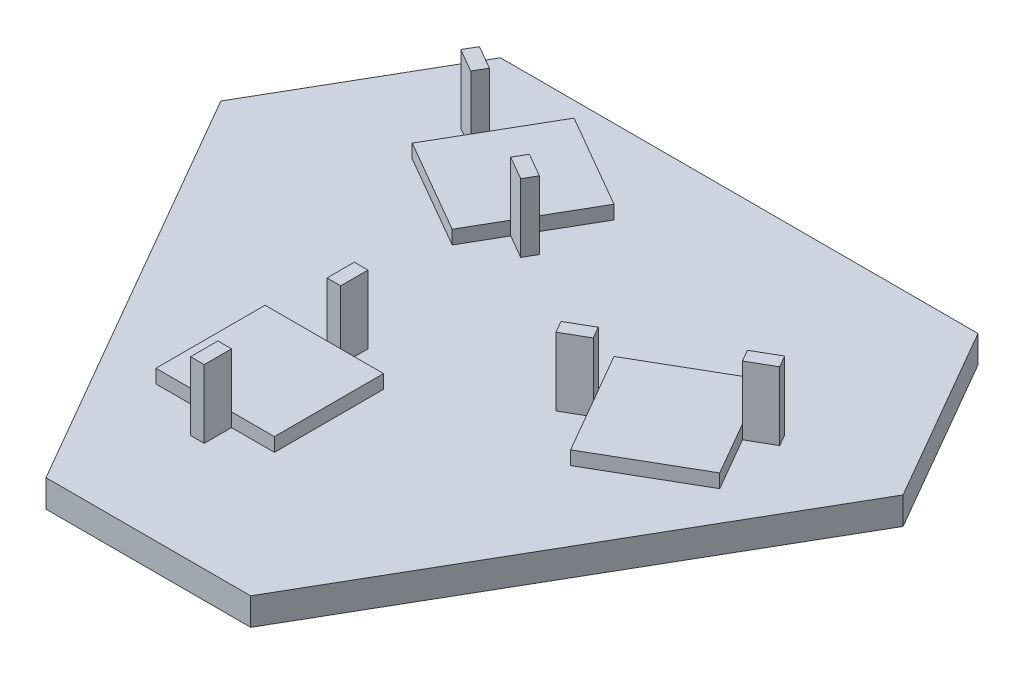
SolidWorks part; units mm, degrees
ref_plane "Front Plane" through (0, 0, 0) normal (0, 0, 1) x (1, 0, 0)
ref_plane "Top Plane" through (0, 0, 0) normal (0, 1, 0) x (1, 0, 0)
ref_plane "Right Plane" through (0, 0, 0) normal (1, 0, 0) x (0, 0, -1)
sketch "Sketch1" plane through (0, 0, 0) normal (0, 1, 0) x (1, 0, 0)
  line L14 (-106.25, 184.0304) -> (81.25, 75.7772) construction
  line L15 (87.5, 216.5064) -> (-87.5, 216.5064)
  line L16 (-87.5, 216.5064) -> (-125, 151.5544)
  line L17 (-125, 151.5544) -> (-37.5, 0)
  line L18 (-37.5, 0) -> (37.5, 0)
  line L19 (37.5, 0) -> (125, 151.5544)
  line L20 (125, 151.5544) -> (87.5, 216.5064)
  line L21 (106.25, 184.0304) -> (-81.25, 75.7772) construction
  line L22 (0, 216.5064) -> (0, 0) construction
  line L23 (87.5, 216.5064) -> (-37.5, 0) construction
  line L24 (-87.5, 216.5064) -> (37.5, 0) construction
  line L25 (125, 151.5544) -> (-125, 151.5544) construction
  point P1 (0, 216.5064)
  point P8 (0, 122.6869)
  dimension "D1" = 175
  dimension "D2" = 75
  dimension "D3" = 120
extrude "Boss-Extrude1" add sketch "Sketch1" along normal blind 10
sketch "Sketch2" plane through (0, 10, 0) normal (0, 1, 0) x (1, 0, 0)
  line L6 (-87.5, 216.5064) -> (-125, 151.5544) construction
  line L7 (125, 151.5544) -> (87.5, 216.5064) construction
  line L8 (-37.5, 0) -> (37.5, 0) construction
  line L16 (-36.9173, 148.2591) -> (-15.2173, 185.8446)
  line L17 (-36.9173, 148.2591) -> (-71.5583, 168.2591)
  line L18 (-15.2173, 185.8446) -> (-49.8583, 205.8446)
  line L19 (-71.5583, 168.2591) -> (-49.8583, 205.8446)
  line L20 (87.5, 216.5064) -> (-100, 108.2532) construction
  line L21 (-3.6875, 89.8727) -> (-47.0875, 89.8727)
  line L22 (-3.6875, 89.8727) -> (-3.6875, 49.8727)
  line L23 (-47.0875, 89.8727) -> (-47.0875, 49.8727)
  line L24 (-3.6875, 49.8727) -> (-47.0875, 49.8727)
  line L25 (87.5, 216.5064) -> (-87.5, 216.5064) construction
  line L26 (33.0863, 137.5314) -> (54.7863, 99.9459)
  line L27 (33.0863, 137.5314) -> (67.7273, 157.5314)
  line L28 (54.7863, 99.9459) -> (89.4273, 119.9459)
  line L29 (67.7273, 157.5314) -> (89.4273, 119.9459)
  line L30 (-37.5, 0) -> (-37.5, 216.5064) construction
  line L31 (-63.7083, 181.8557) -> (-72.3686, 186.8557)
  line L32 (-63.7083, 181.8557) -> (-61.2083, 186.1858)
  line L33 (-72.3686, 186.8557) -> (-69.8686, 191.1858)
  line L34 (-61.2083, 186.1858) -> (-69.8686, 191.1858)
  line L35 (-29.0673, 161.8557) -> (-20.407, 156.8557)
  line L36 (-29.0673, 161.8557) -> (-26.5673, 166.1858)
  line L37 (-20.407, 156.8557) -> (-17.907, 161.1858)
  line L38 (-26.5673, 166.1858) -> (-17.907, 161.1858)
  line L39 (84.2376, 148.9348) -> (75.5773, 143.9348)
  line L40 (84.2376, 148.9348) -> (86.7376, 144.6046)
  line L41 (75.5773, 143.9348) -> (78.0773, 139.6046)
  line L42 (86.7376, 144.6046) -> (78.0773, 139.6046)
  line L43 (32.2761, 118.9348) -> (40.9363, 123.9348)
  line L44 (32.2761, 118.9348) -> (34.7761, 114.6046)
  line L45 (40.9363, 123.9348) -> (43.4363, 119.6046)
  line L46 (34.7761, 114.6046) -> (43.4363, 119.6046)
  line L47 (-19.3875, 99.8727) -> (-19.3875, 89.8727)
  line L48 (-19.3875, 99.8727) -> (-24.3875, 99.8727)
  line L49 (-19.3875, 89.8727) -> (-24.3875, 89.8727)
  line L50 (-24.3875, 99.8727) -> (-24.3875, 89.8727)
  line L51 (-19.3875, 49.8727) -> (-19.3875, 39.8727)
  line L52 (-19.3875, 49.8727) -> (-24.3875, 49.8727)
  line L53 (-19.3875, 39.8727) -> (-24.3875, 39.8727)
  line L54 (-24.3875, 49.8727) -> (-24.3875, 39.8727)
  line L55 (-125, 151.5544) -> (-37.5, 0) construction
  line L56 (-87.5, 216.5064) -> (100, 108.2532) construction
  line L57 (37.5, 0) -> (125, 151.5544) construction
  dimension "D1" = 5
  dimension "D2" = 10
  dimension "D3" = 37.9295
  dimension "D4" = 46.6111
  dimension "D5" = 49.8727
  dimension "D6" = 40
  dimension "D7" = 43.4
  dimension "D8" = 22.7
  dimension "D9" = 22.7
  dimension "D10" = 22.7
  dimension "D11" = 22.7
  dimension "D12" = 22.7
  dimension "D13" = 22.7
  dimension "D14" = 33.8125
  dimension "D15" = 41.1875
  dimension "D16" = 9.5875
extrude "Boss-Extrude2" add sketch "Sketch2" along normal blind 5 contours L19 L17 L16 L18 | L24 L22 L21 L23 | L29 L27 L26 L28 region at (-43.3878, 10, -177.0519) region at (-25.3875, 10, -69.8727) region at (61.2568, 10, -128.7386)
extrude "Boss-Extrude3" add sketch "Sketch2<3>" along normal blind 25 contours L19 L34 L33 L31 | L38 L16 L35 L37 | L48 L50 L21 L47 | L24 L54 L53 L51 | L44 L46 L26 L43 | L42 L40 L39 L29 region at (-23.4872, 10, -161.5208) region at (-66.7884, 10, -186.5208) region at (-21.8875, 10, -94.8727) region at (-21.8875, 10, -44.8727) region at (37.8562, 10, -119.2697) region at (81.1575, 10, -144.2697)
sketch "Sketch2<3>" plane through (0, 10, 0) normal (0, 1, 0) x (1, 0, 0) same geometry as "Sketch2"
